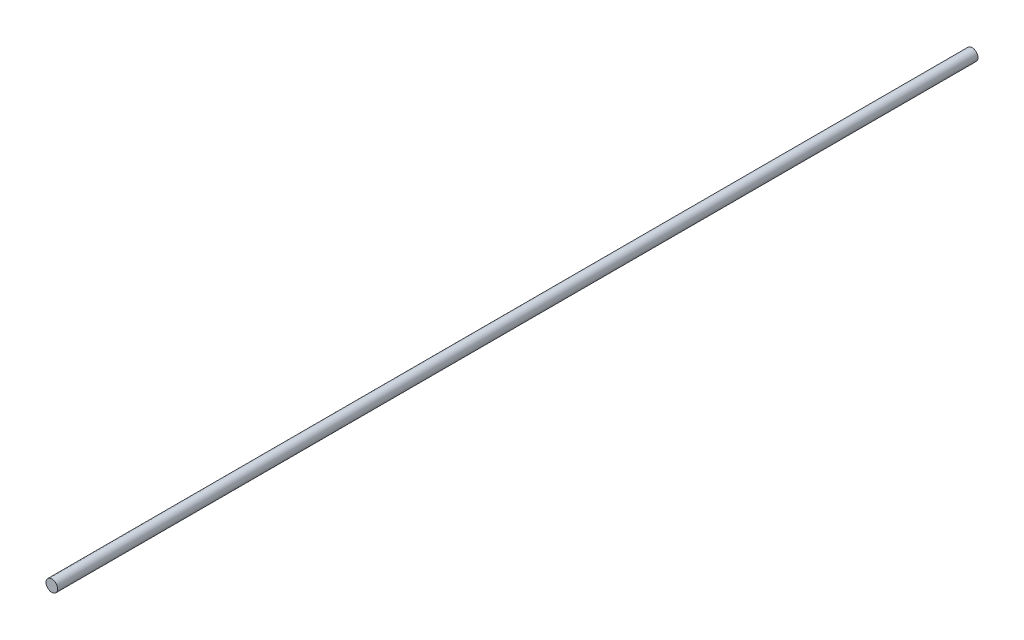
SolidWorks part; units mm, degrees
material "6061-T6 (SS)"
ref_plane "Front" through (0, 0, 0) normal (0, 0, 1) x (1, 0, 0)
ref_plane "Top" through (0, 0, 0) normal (0, 1, 0) x (1, 0, 0)
ref_plane "Right" through (0, 0, 0) normal (1, 0, 0) x (0, 0, -1)
sketch "Sketch1" plane through (0, 0, 0) normal (0, 0, 1) x (1, 0, 0)
  circle A0 centre (0, 0) radius 3.175
  dimension "D1" = 6.35
extrude "Boss-Extrude1" add sketch "Sketch1" along normal blind 501.65
